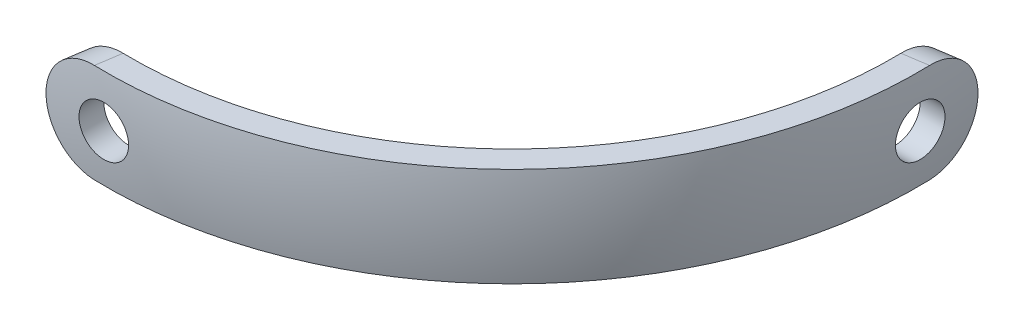
SolidWorks part; units mm, degrees
ref_plane "前视基准面" through (0, 0, 0) normal (0, 0, 1) x (1, 0, 0)
ref_plane "上视基准面" through (0, 0, 0) normal (0, 1, 0) x (1, 0, 0)
ref_plane "右视基准面" through (0, 0, 0) normal (1, 0, 0) x (0, 0, -1)
sketch "草图2" plane through (0, 0, 0) normal (0, 0, 1) x (1, 0, 0)
  line L0 (0, 0) -> (66, 0) construction
  line L1 (61.4817, 8) -> (65.5134, 8)
  line L2 (0, 0) -> (0, 18.8305) construction
  line L3 (65.5134, -8) -> (61.4817, -8)
  arc A0 (61.4817, -8) -> (61.4817, 8) centre (0, 0) ccw
  arc A1 (65.5134, -8) -> (65.5134, 8) centre (0, 0) ccw
  dimension "D1" = 8
  dimension "D3" = 62
  dimension "D4" = 66
  dimension "D2" = 8
revolve "旋转1" add sketch "草图2" angle 98.681 about L2
sketch "草图3" plane through (0, 0, 0) normal (0, 0, 1) x (1, 0, 0)
  circle A0 centre (0, 0) radius 4
extrude "切除-拉伸1" cut sketch "草图3" along normal through all
sketch "草图4" plane through (0, 0, 0) normal (1, 0, 0) x (0, 0, -1)
  circle A0 centre (0, 0) radius 4
extrude "切除-拉伸2" cut sketch "草图4" along normal through all
fillet "圆角1" radius 8 4 edges at (-9.5841, 8, 62.7701) (62.7701, -8, -9.5841) (62.7701, 8, -9.5841) (-9.5841, -8, 62.7701)
